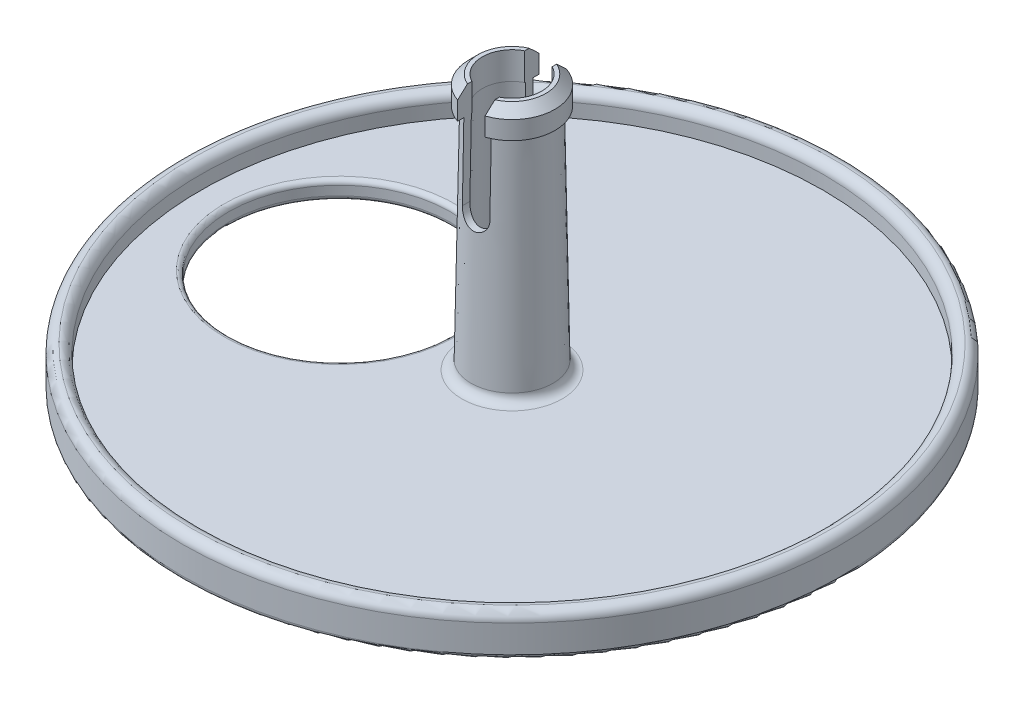
SolidWorks part; units mm, degrees
ref_plane "Front" through (0, 0, 0) normal (0, 0, 1) x (1, 0, 0)
ref_plane "Top" through (0, 0, 0) normal (0, 1, 0) x (1, 0, 0)
ref_plane "Right" through (0, 0, 0) normal (1, 0, 0) x (0, 0, -1)
sketch "Sketch1" plane through (0, 0, 0) normal (0, 1, 0) x (1, 0, 0)
  circle A0 centre (0, 0) radius 36
  dimension "D1" = 72
extrude "Boss-Extrude1" add sketch "Sketch1" along normal blind 4.5
shell "Shell1" thickness 2 removed face at (0, 4.5, 36)
sketch "Sketch2" plane through (0, 2, 0) normal (0, 1, 0) x (1, 0, 0)
  circle A0 centre (0, 0) radius 4.5
  circle A1 centre (0, 0) radius 3.25
  dimension "D1" = 9
  dimension "D2" = 1.25
extrude "Boss-Extrude2" add sketch "Sketch2" along normal blind 28 draft 1.023 contours A0
sketch "Sketch3" plane through (0, 0, 0) normal (0, 0, 1) x (1, 0, 0)
  line L0 (0, 18.75) -> (0, 30) construction
  line L1 (-1.5, 18.75) -> (-1.5, 30)
  line L2 (1.5, 18.75) -> (1.5, 30)
  line L3 (4, 30) -> (-4, 30) construction
  arc A0 (-1.5, 18.75) -> (1.5, 18.75) centre (0, 18.75) ccw
  arc A1 (1.5, 30) -> (-1.5, 30) centre (0, 30) ccw
  point P3 (0, 24.375)
  point P8 (0, 30)
  point P11 (0, 17.25)
  dimension "D1" = 3
  dimension "D2" = 12.75
extrude "Cut-Extrude1" cut sketch "Sketch3" against normal blind 28 and the other way blind 28
sketch "Sketch5" plane through (0, 2, 0) normal (0, 1, 0) x (1, 0, 0)
  circle A0 centre (0, 0) radius 3.75
  dimension "D1" = 7.5
extrude "Cut-Extrude2" cut sketch "Sketch5" along normal blind 28 draft 1.023
fillet "Fillet1" radius 1 1 edges at (0, 2, 3.75)
fillet "Fillet2" radius 1 2 edges at (0, 4.5, 36) (0, 4.5, 34)
sketch "Sketch6" plane through (0, 30, 0) normal (0, 1, 0) x (1, 0, 0)
  line L0 (1.5, 2.8832) -> (1.5, 4.4444)
  line L1 (-1.5, 2.8832) -> (-1.5, 4.4444)
  line L2 (-1.5, -2.8832) -> (-1.5, -4.4444)
  line L3 (1.5, -2.8832) -> (1.5, -4.4444)
  arc A0 (-1.5, 4.4444) -> (-1.5, -4.4444) centre (0, 0) ccw
  arc A1 (-1.5, 2.8832) -> (-1.5, -2.8832) centre (0, 0) ccw
  arc A2 (1.5, -2.8832) -> (1.5, 2.8832) centre (0, 0) ccw
  arc A3 (1.5, -4.4444) -> (1.5, 4.4444) centre (0, 0) ccw
extrude "Boss-Extrude3" add sketch "Sketch6" against normal blind 3
chamfer "Chamfer1" distance 1 angle 45 2 edges at (4.6907, 30, 0) (-4.6907, 30, 0)
sketch "Sketch8" plane through (0, 2, 0) normal (0, 1, 0) x (1, 0, 0)
  circle A0 centre (-18.85, 0) radius 12.1
  circle A1 centre (0, 0) radius 34 construction
  point P4 (-18.8213, 1.0391)
  dimension "D1" = 24.2
  dimension "D2" = 18.85
extrude "Cut-Extrude3" cut sketch "Sketch8" against normal blind 10
fillet "Fillet3" radius 0.5 3 edges at (-18.85, 2, 12.1) (0, 0, 36) (-18.85, 0, 12.1)
fillet "Fillet4" radius 1 1 edges at (0, 2, 4.5)
